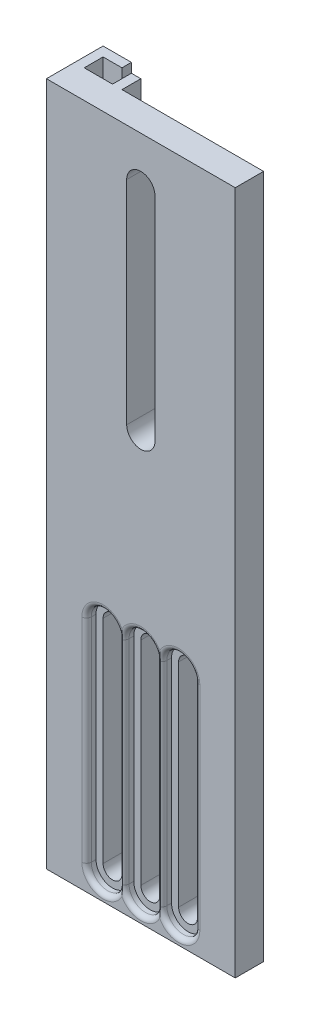
SolidWorks part; units mm, degrees
ref_plane "Спереди" through (0, 0, 0) normal (0, 0, 1) x (1, 0, 0)
ref_plane "Сверху" through (0, 0, 0) normal (0, 1, 0) x (1, 0, 0)
ref_plane "Справа" through (0, 0, 0) normal (1, 0, 0) x (0, 0, -1)
sketch "Эскиз1" plane through (0, 0, 0) normal (0, 0, 1) x (1, 0, 0)
  line L1 (-20, 80) -> (20, 80)
  line L2 (-20, 80) -> (-20, -80)
  line L3 (-20, -80) -> (20, -80)
  line L4 (20, 80) -> (20, -80)
  line L5 (-20, 80) -> (20, -80) construction
  line L6 (-20, -80) -> (20, 80) construction
  point P0 (0, 0)
  dimension "D1" = 40
  dimension "D2" = 160
extrude "Бобышка-Вытянуть2" add sketch "Эскиз1" along normal blind 6
sketch "Эскиз3" plane through (0, 0, 6) normal (0, 0, 1) x (1, 0, 0)
  line L0 (-20, -80) -> (-20, 20)
  line L1 (-20, 80) -> (-20, -80) construction
  line L2 (0, 80) -> (0, 58)
  line L3 (20, 80) -> (-20, 80) construction
  line L5 (-3, 55) -> (-3, 10)
  line L6 (3, 55) -> (3, 10)
  arc A0 (3, 55) -> (-3, 55) centre (0, 55) ccw
  arc A1 (-3, 10) -> (3, 10) centre (0, 10) ccw
  dimension "D3" = 6
  dimension "D1" = 100
  dimension "D2" = 25
  dimension "D4" = 45
sketch "Эскиз5" plane through (0, 0, 6) normal (0, 0, 1) x (1, 0, 0)
  line L0 (-20, 80) -> (-20, 65)
  line L1 (-20, 80) -> (-20, -80) construction
  line L2 (-20, 65) -> (20, 65)
  line L3 (20, -80) -> (20, 80) construction
  line L4 (20, 65) -> (20, 80)
  line L5 (20, 80) -> (-20, 80)
  dimension "D1" = 15
extrude "Вырез-Вытянуть3" cut sketch "Эскиз3" against normal blind 10 contours L5 A1 L6 A0
extrude "Вырез-Вытянуть4" cut sketch "Эскиз5" against normal blind 10
sketch "Эскиз7" plane through (0, 0, 6) normal (0, 0, 1) x (1, 0, 0)
  line L0 (-20, -80) -> (-8, -80)
  line L1 (-20, -80) -> (20, -80) construction
  line L2 (-8, -80) -> (-8, -75)
  line L3 (0, -80) -> (0, -75)
  line L4 (8, -80) -> (8, -75)
  line L5 (20, -80) -> (8, -80)
  line L7 (-8, -52.5) -> (-6, -52.5)
  line L8 (8, -25) -> (8, -30)
  line L9 (0, -25) -> (0, -28)
  line L10 (-8, -25) -> (-8, -28)
  line L11 (-10, -30) -> (-10, -75)
  line L12 (-6, -30) -> (-6, -75)
  line L13 (-2, -75) -> (-2, -30)
  line L15 (2, -75) -> (6, -75)
  line L16 (6, -75) -> (6, -30)
  line L17 (6, -30) -> (2, -30)
  line L18 (2, -75) -> (2, -30)
  line L19 (10, -30) -> (10, -75)
  arc A0 (-10, -75) -> (-6, -75) centre (-8, -75) ccw
  arc A1 (10, -75) -> (6, -75) centre (8, -75) cw
  arc A2 (-2, -75) -> (2, -75) centre (0, -75) ccw
  arc A3 (-2, -30) -> (2, -30) centre (0, -30) cw
  arc A4 (10, -30) -> (6, -30) centre (8, -30) ccw
  arc A5 (-10, -30) -> (-6, -30) centre (-8, -30) cw
  dimension "D3" = 4
  dimension "D1" = 12
  dimension "D2" = 5
  dimension "D4" = 45
extrude "Вырез-Вытянуть5" cut sketch "Эскиз7" against normal blind 10
sketch "Эскиз8" plane through (0, 0, 6) normal (0, 0, 1) x (1, 0, 0)
  line L0 (-10, -52.5) -> (-7.0633, -52.5)
  line L1 (-10, -30) -> (-10, -75) construction
  line L2 (-11.5, -75) -> (-11.5, -30)
  line L3 (-4.5, -75) -> (-4.5, -30)
  line L4 (-4.5, -30) -> (-3.5, -30)
  line L5 (-3.5, -30) -> (-3.5, -75)
  line L6 (3.5, -30) -> (3.5, -75)
  line L7 (3.5, -75) -> (4.5, -75)
  line L8 (4.5, -75) -> (4.5, -30)
  line L9 (11.5, -30) -> (11.5, -75)
  arc A0 (-11.5, -75) -> (-4.5, -75) centre (-8, -75) ccw
  arc A1 (-3.5, -75) -> (3.5, -75) centre (0, -75) ccw
  arc A2 (4.5, -75) -> (11.5, -75) centre (8, -75) ccw
  arc A3 (4.5, -30) -> (11.5, -30) centre (8, -30) cw
  arc A4 (-3.5, -30) -> (3.5, -30) centre (0, -30) cw
  arc A5 (-11.5, -30) -> (-4.5, -30) centre (-8, -30) cw
  arc M2 (-10, -30) -> (-6, -30) centre (-8, -30) cw
  line M3 (-6, -30) -> (-6, -75)
  arc M4 (-6, -75) -> (-10, -75) centre (-8, -75) cw
  line M5 (-10, -75) -> (-10, -30)
  line M14 (-2, -75) -> (-2, -30)
  arc M15 (-2, -30) -> (2, -30) centre (0, -30) cw
  line M16 (2, -30) -> (2, -75)
  arc M17 (2, -75) -> (-2, -75) centre (0, -75) cw
  arc M18 (6, -30) -> (10, -30) centre (8, -30) cw
  line M19 (10, -30) -> (10, -75)
  arc M20 (10, -75) -> (6, -75) centre (8, -75) cw
  line M21 (6, -75) -> (6, -30)
  dimension "D1" = 7
  dimension "D2" = 7
extrude "Вырез-Вытянуть6" cut sketch "Эскиз8" against normal blind 2 contours A5 L2 A0 L3 M5 M2 M3 M4 | A4 L5 A1 L6 M17 M14 M15 M16 | A3 L8 A2 L9 M21 M18 M19 M20
fillet "Скругление1" radius 1 12 edges at (-8, -78.5, 6) (-4.5, -52.5, 6) (-8, -26.5, 6) (0, -26.5, 6) (3.5, -52.5, 6) (0, -78.5, 6) (8, -26.5, 6) (4.5, -52.5, 6) (8, -78.5, 6) (-11.5, -52.5, 6) (-3.5, -52.5, 6) (11.5, -52.5, 6)
sketch "Эскиз10" plane through (0, 0, 0) normal (0, 0, -1) x (-1, 0, 0)
  line L1 (20, 65) -> (10, 65)
  line L2 (20, 65) -> (20, 5)
  line L3 (20, 5) -> (10, 5)
  line L4 (10, 65) -> (10, 5)
  dimension "D1" = 60
  dimension "D2" = 10
extrude "Бобышка-Вытянуть3" add sketch "Эскиз10" along normal blind 4
sketch "Эскиз11" plane through (0, 0, -4) normal (0, 0, -1) x (-1, 0, 0)
  line L0 (10, 65) -> (12, 65)
  line L1 (20, 65) -> (10, 65) construction
  line L2 (12, 65) -> (12, 5)
  line L3 (10, 5) -> (20, 5) construction
  line L4 (12, 5) -> (18, 5)
  line L5 (18, 5) -> (18, 65)
  line L6 (18, 65) -> (20, 65)
  line L7 (12, 65) -> (18, 65)
  line M4 (20, 65) -> (10, 65)
  line M6 (10, 5) -> (20, 5)
  dimension "D1" = 2
extrude "Вырез-Вытянуть7" cut sketch "Эскиз11" against normal blind 4 contours L5 L2 M6 M4
sketch "Эскиз13" plane through (0, 0, -4) normal (0, 0, -1) x (-1, 0, 0)
  line L0 (12, 65) -> (12, 5) construction
  line L1 (20, 65) -> (14, 65)
  line L2 (20, 65) -> (20, 36)
  line L3 (20, 36) -> (14, 36)
  line L4 (14, 65) -> (14, 36)
  line L5 (18, 5) -> (18, 65) construction
  line L6 (10, 5) -> (16, 5)
  line L7 (10, 5) -> (10, 34)
  line L8 (10, 34) -> (16, 34)
  line L9 (16, 5) -> (16, 34)
  dimension "D1" = 29
  dimension "D2" = 2
  dimension "D3" = 2
  dimension "D4" = 29
extrude "Бобышка-Вытянуть9" add sketch "Эскиз13" along normal blind 2
